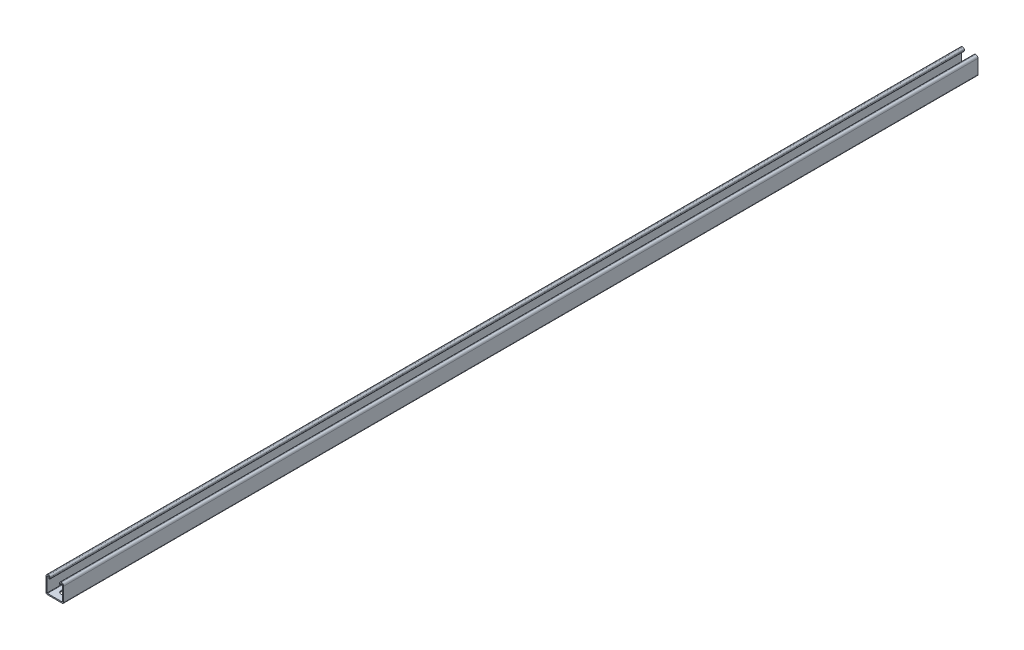
SolidWorks part; units mm, degrees
ref_plane "Front Plane" through (0, 0, 0) normal (0, 0, 1) x (1, 0, 0)
ref_plane "Top Plane" through (0, 0, 0) normal (0, 1, 0) x (1, 0, 0)
ref_plane "Right Plane" through (0, 0, 0) normal (1, 0, 0) x (0, 0, -1)
sketch "Sketch1" plane through (0, 0, 0) normal (0, 0, 1) x (1, 0, 0)
  line L0 (-20.6377, 0) -> (-17.9706, 0) construction
  line L1 (20.6377, 0) -> (17.9706, 0) construction
  line L2 (17.1769, -17.9704) -> (-17.1769, -17.9704)
  line L3 (-17.9706, -17.1766) -> (-17.9706, 15.5891)
  line L4 (-15.5894, 17.9704) -> (-14.5734, 17.9704)
  line L5 (-13.7797, 17.1766) -> (-13.7797, 14.8335)
  line L6 (-11.1127, 14.8335) -> (-11.1127, 17.1766)
  line L7 (-14.5734, 20.6374) -> (-15.5894, 20.6374)
  line L8 (-20.6377, 15.5891) -> (-20.6377, -17.1766)
  line L9 (-17.1769, -20.6374) -> (17.1769, -20.6374)
  line L10 (20.6377, 15.5891) -> (20.6377, -17.1766)
  line L11 (14.5734, 20.6374) -> (15.5894, 20.6374)
  line L12 (11.1127, 14.8335) -> (11.1127, 17.1766)
  line L13 (13.7797, 17.1766) -> (13.7797, 14.8335)
  line L14 (0, -17.9704) -> (0, -20.6374) construction
  line L15 (15.5894, 17.9704) -> (14.5734, 17.9704)
  line L16 (17.9706, -17.1766) -> (17.9706, 15.5891)
  arc A0 (-17.1769, -20.6374) -> (-20.6377, -17.1766) centre (-17.1769, -17.1766) cw
  arc A1 (-17.1769, -17.9704) -> (-17.9706, -17.1766) centre (-17.1769, -17.1766) cw
  arc A2 (-17.9706, 15.5891) -> (-15.5894, 17.9704) centre (-15.5894, 15.5891) cw
  arc A3 (-20.6377, 15.5891) -> (-15.5894, 20.6374) centre (-15.5894, 15.5891) cw
  arc A4 (-14.5734, 17.9704) -> (-13.7797, 17.1766) centre (-14.5734, 17.1766) cw
  arc A5 (-14.5734, 20.6374) -> (-11.1127, 17.1766) centre (-14.5734, 17.1766) cw
  arc A6 (-13.7797, 14.8335) -> (-11.1127, 14.8335) centre (-12.4462, 14.8335) ccw
  arc A7 (13.7797, 14.8335) -> (11.1127, 14.8335) centre (12.4462, 14.8335) cw
  arc A8 (14.5734, 20.6374) -> (11.1127, 17.1766) centre (14.5734, 17.1766) ccw
  arc A9 (14.5734, 17.9704) -> (13.7797, 17.1766) centre (14.5734, 17.1766) ccw
  arc A10 (20.6377, 15.5891) -> (15.5894, 20.6374) centre (15.5894, 15.5891) ccw
  arc A11 (17.9706, 15.5891) -> (15.5894, 17.9704) centre (15.5894, 15.5891) ccw
  arc A12 (17.1769, -17.9704) -> (17.9706, -17.1766) centre (17.1769, -17.1766) ccw
  arc A13 (17.1769, -20.6374) -> (20.6377, -17.1766) centre (17.1769, -17.1766) ccw
  dimension "D4" = 3.4608
  dimension "D5" = 5.0483
  dimension "D7" = 3.4608
  dimension "D1" = 34.3538
  dimension "D2" = 41.2748
  dimension "D3" = 2.667
  dimension "D6" = 1.016
  dimension "D8" = 2.3432
extrude "Primary Extrusion" add sketch "Sketch1" against normal blind 2133.6
sketch "Sketch58" plane through (0, -20.6374, 0) normal (0, 1, 0) x (-1, 0, 0)
  line L0 (7.1438, -29.3687) -> (7.1438, -21.4313)
  line L1 (-7.1438, -21.4313) -> (-7.1438, -29.3687)
  line L2 (0, 22.7012) -> (0, -22.7012) construction
  line L3 (-7.1438, -25.4) -> (7.1438, -25.4) construction
  line L4 (17.1769, 0) -> (-17.1769, 0) construction
  arc A0 (7.1438, -29.3687) -> (-7.1438, -29.3687) centre (0, -29.3687) cw
  arc A1 (-7.1438, -21.4313) -> (7.1438, -21.4313) centre (0, -21.4313) cw
  point P12 (0, -36.5125)
  point P13 (0, -14.2875)
  dimension "D2" = 22.225
  dimension "D1" = 14.2875
  dimension "D3" = 25.4
extrude "Slot Cut" cut sketch "Sketch58" along normal up to next contours L0 A1 L1 A0
pattern_linear "LPattern1" count 42 spacing 50.8 along (0, 0, -1) of "Slot Cut"
ref_plane "Center Plane" through (0, 0, -1066.8) normal (0, 0, -1) x (-1, 0, 0)
